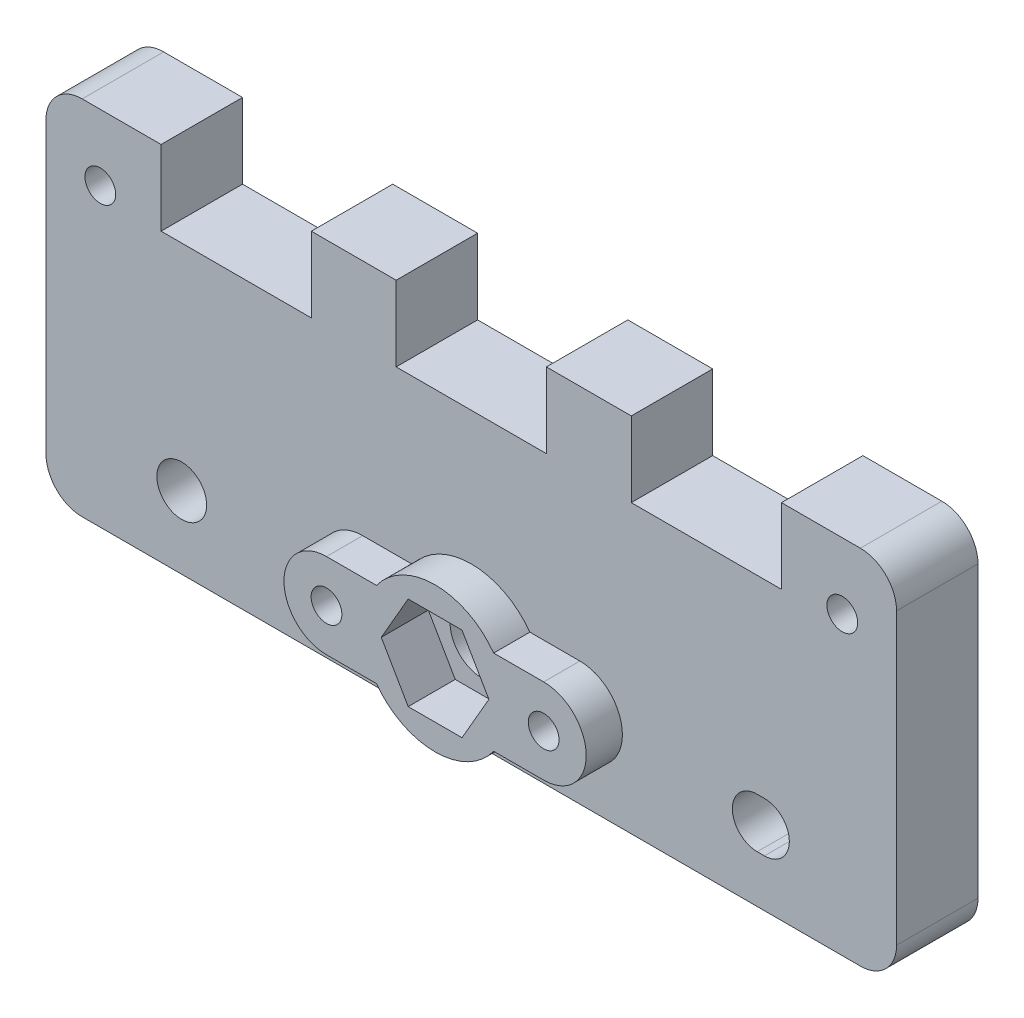
SolidWorks part; units mm, degrees
ref_plane "Front Plane" through (0, 0, 0) normal (0, 0, 1) x (1, 0, 0)
ref_plane "Top Plane" through (0, 0, 0) normal (0, 1, 0) x (1, 0, 0)
ref_plane "Right Plane" through (0, 0, 0) normal (1, 0, 0) x (0, 0, -1)
sketch "S01 - Common slider blank" plane through (0, 0, 0) normal (0, 0, 1) x (1, 0, 0)
  line L0 (-43, -91) -> (43, -91)
  line L1 (47, -87) -> (47, -55)
  line L2 (43, -51) -> (-43, -51)
  line L3 (-47, -55) -> (-47, -87)
  arc A0 (43, -91) -> (47, -87) centre (43, -87) ccw
  arc A1 (47, -55) -> (43, -51) centre (43, -55) ccw
  arc A2 (-43, -51) -> (-47, -55) centre (-43, -55) ccw
  arc A3 (-47, -87) -> (-43, -91) centre (-43, -87) ccw
  dimension "D1" = 4
  dimension "D2" = 47
  dimension "D3" = 47
  dimension "D4" = 51
  dimension "D5" = 91
extrude "01 - Common slider blank" add sketch "S01 - Common slider blank" along normal blind 9
sketch "S02 - Round locating guide and relieved companion" plane through (0, 0, 0) normal (0, 0, 1) x (1, 0, 0)
  line L0 (31.6, -80.25) -> (32.4, -80.25)
  line L1 (32.4, -85.75) -> (31.6, -85.75)
  circle A0 centre (-32, -83) radius 2.75
  arc A1 (32.4, -80.25) -> (32.4, -85.75) centre (32.4, -83) cw
  arc A2 (31.6, -85.75) -> (31.6, -80.25) centre (31.6, -83) cw
  dimension "D1" = 5.5
  dimension "D2" = 31.6
  dimension "D3" = 32.4
  dimension "D4" = 32
  dimension "D5" = 83
extrude "02 - Round locating guide and relieved companion" cut sketch "S02 - Round locating guide and relieved companion" along normal blind 10 from offset 0.5 offset against normal yes
sketch "S03 - Three drop-in spring seats" plane through (0, 0, 0) normal (0, 0, 1) x (1, 0, 0)
  line L0 (-34.2808, -59.3) -> (-17.6808, -59.3)
  line L1 (-17.6808, -59.3) -> (-17.6808, -50)
  line L2 (-17.6808, -50) -> (-34.2808, -50)
  line L3 (-34.2808, -50) -> (-34.2808, -59.3)
  line L4 (17.6808, -59.3) -> (34.2808, -59.3)
  line L5 (34.2808, -59.3) -> (34.2808, -50)
  line L6 (34.2808, -50) -> (17.6808, -50)
  line L7 (17.6808, -50) -> (17.6808, -59.3)
  line L8 (-8.3, -59.3) -> (8.3, -59.3)
  line L9 (8.3, -59.3) -> (8.3, -50)
  line L10 (8.3, -50) -> (-8.3, -50)
  line L11 (-8.3, -50) -> (-8.3, -59.3)
  dimension "D1" = 8.3
  dimension "D2" = 17.6808
  dimension "D3" = 34.2808
  dimension "D4" = 8.3
  dimension "D5" = 17.6808
  dimension "D6" = 34.2808
  dimension "D7" = 50
  dimension "D8" = 59.3
extrude "03 - Three drop-in spring seats" cut sketch "S03 - Three drop-in spring seats" along normal blind 10 from offset 0.5 offset against normal yes
sketch "S04 - Keeper screw holes" plane through (0, 0, 0) normal (0, 0, 1) x (1, 0, 0)
  circle A0 centre (-41, -58.3) radius 1.7
  circle A1 centre (41, -58.3) radius 1.7
  dimension "D1" = 3.4
  dimension "D2" = 3.4
  dimension "D3" = 41
  dimension "D4" = 41
  dimension "D5" = 58.3
extrude "04 - Keeper screw holes" cut sketch "S04 - Keeper screw holes" along normal blind 10 from offset 0.5 offset against normal yes
sketch "S05 - Rear nut housing with fastening bosses" plane through (0, 0, 0) normal (0, 0, 1) x (1, 0, 0)
  line L0 (-12, -77.3) -> (12, -77.3)
  line L1 (12, -86.7) -> (-12, -86.7)
  arc A0 (12, -77.3) -> (12, -86.7) centre (12, -82) cw
  arc A1 (-12, -86.7) -> (-12, -77.3) centre (-12, -82) cw
  dimension "D1" = 4.7
  dimension "D2" = 12
  dimension "D3" = 12
  dimension "D4" = 82
extrude "05 - Rear nut housing with fastening bosses" add sketch "S05 - Rear nut housing with fastening bosses" along normal blind 4.2 from offset 8.8
sketch "S06 - Central working nut surround" plane through (0, 0, 0) normal (0, 0, 1) x (1, 0, 0)
  circle A0 centre (0, -82) radius 8
  dimension "D1" = 16
  dimension "D2" = 82
extrude "06 - Central working nut surround" add sketch "S06 - Central working nut surround" along normal blind 4.2 from offset 8.8
sketch "S07 - Clearance tunnel for rotating spindle retainer" plane through (0, 0, 0) normal (0, 0, 1) x (1, 0, 0)
  circle A0 centre (0, -82) radius 7.35
  dimension "D1" = 14.7
  dimension "D2" = 82
extrude "07 - Clearance tunnel for rotating spindle retainer" cut sketch "S07 - Clearance tunnel for rotating spindle retainer" along normal blind 6.15 from offset 0.15 offset against normal yes
sketch "S08 - Bolt passage through thrust land" plane through (0, 0, 0) normal (0, 0, 1) x (1, 0, 0)
  circle A0 centre (0, -82) radius 3.55
  dimension "D1" = 7.1
  dimension "D2" = 82
extrude "08 - Bolt passage through thrust land" cut sketch "S08 - Bolt passage through thrust land" along normal blind 13.3 from offset 0.1 offset against normal yes
sketch "S09 - Rear-opening AF10 hex nut trap" plane through (0, 0, 0) normal (0, 0, 1) x (1, 0, 0)
  line L0 (5.9467, -82) -> (2.9734, -76.85)
  line L1 (2.9734, -76.85) -> (-2.9734, -76.85)
  line L2 (-2.9734, -76.85) -> (-5.9467, -82)
  line L3 (-5.9467, -82) -> (-2.9734, -87.15)
  line L4 (-2.9734, -87.15) -> (2.9734, -87.15)
  line L5 (2.9734, -87.15) -> (5.9467, -82)
  dimension "D1" = 2.9734
  dimension "D2" = 5.9467
  dimension "D3" = 2.9734
  dimension "D4" = 5.9467
  dimension "D5" = 76.85
  dimension "D6" = 82
  dimension "D7" = 87.15
extrude "09 - Rear-opening AF10 hex nut trap" cut sketch "S09 - Rear-opening AF10 hex nut trap" along normal blind 5.4 from offset 7.8
sketch "S10 - Nut keeper fastener passages" plane through (0, 0, 0) normal (0, 0, 1) x (1, 0, 0)
  circle A0 centre (-12, -82) radius 1.7
  circle A1 centre (12, -82) radius 1.7
  dimension "D1" = 3.4
  dimension "D2" = 3.4
  dimension "D3" = 12
  dimension "D4" = 12
  dimension "D5" = 82
extrude "10 - Nut keeper fastener passages" cut sketch "S10 - Nut keeper fastener passages" along normal blind 13.3 from offset 0.1 offset against normal yes
